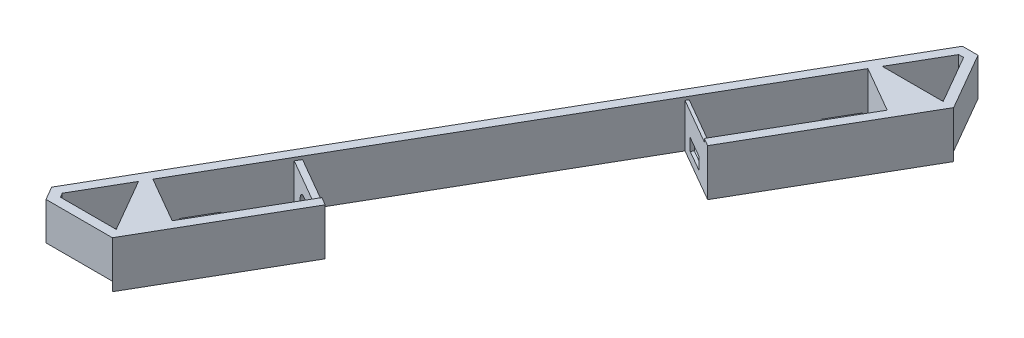
SolidWorks part; units mm, degrees
ref_plane "Front Plane" through (0, 0, 0) normal (0, 0, 1) x (1, 0, 0)
ref_plane "Top Plane" through (0, 0, 0) normal (0, 1, 0) x (1, 0, 0)
ref_plane "Right Plane" through (0, 0, 0) normal (1, 0, 0) x (0, 0, -1)
sketch "Sketch1" plane through (0, 0, 0) normal (0, 1, 0) x (1, 0, 0)
  line L24 (-11.7321, 167.8653) -> (3.2679, 159.2051)
  line L29 (3.2679, 159.2051) -> (-18.2321, 121.966) construction
  line L31 (-107.8246, -1.4282) -> (-108.6491, 0)
  line L40 (-0.8246, 186.7576) -> (0.8246, 186.7576)
  line L41 (-109.5566, -4.4282) -> (-112.1132, 0)
  line L42 (-2.5566, 189.7576) -> (-112.1132, 0)
  line L44 (-2.5566, 189.7576) -> (2.5566, 189.7576)
  line L50 (-99.4737, 15.8923) -> (-89.4737, -1.4282)
  line L51 (-107.8246, -1.4282) -> (-89.4737, -1.4282)
  line L52 (-99.4737, 15.8923) -> (-108.6491, 0)
  line L62 (-10, 170.8653) -> (10, 170.8653)
  line L63 (-10, 170.8653) -> (-0.8246, 186.7576)
  line L64 (0.8246, 186.7576) -> (10, 170.8653)
  line L65 (2.5566, 189.7576) -> (13.4641, 170.8653)
  line L71 (-109.5566, -4.4282) -> (-87.7417, -4.4282)
  line L82 (-39.7369, 84.7186) -> (-37.1388, 83.2186)
  line L96 (13.4641, 170.8653) -> (-16.134, 119.6)
  line L100 (-18.2321, 121.966) -> (-33.2321, 130.6262)
  line L102 (-11.7321, 167.8653) -> (-33.2321, 130.6262)
  line L104 (-33.7321, 129.7602) -> (-97.7417, 18.8923)
  line L111 (-33.7321, 129.7602) -> (-18.7321, 121.1)
  line L113 (-16.134, 119.6) -> (-18.7321, 121.1)
  line L115 (-18.7321, 121.1) -> (-18.2321, 121.966)
  line L117 (-18.2321, 121.966) -> (3.2679, 159.2051)
  line L119 (-33.7321, 129.7602) -> (-33.2321, 130.6262)
  line L121 (-97.7417, 18.8923) -> (-80.7417, 48.3372) construction
  line L123 (-80.7417, 48.3372) -> (-65.7417, 39.6769)
  line L125 (-97.7417, 18.8923) -> (-82.7417, 10.2321)
  line L127 (-82.7417, 10.2321) -> (-65.7417, 39.6769)
  line L133 (-65.7417, 39.6769) -> (-64.7417, 41.409)
  line L134 (-64.7417, 41.409) -> (-79.7417, 50.0692)
  line L135 (-64.7417, 41.409) -> (-62.1436, 39.909)
  line L137 (-87.7417, -4.4282) -> (-62.1436, 39.909)
  dimension "D1" = 43
  dimension "D2" = 34
  dimension "D3" = 2
extrude "Boss-Extrude2" add sketch "Sketch1" along normal blind 15.38 contours L41 L71 L65 L44 L42 L40 L64 L62 L63 L52 L50 L51 L31 region at (-24.4848, 0, -150.4021)
extrude "Boss-Extrude3" add sketch "Sketch1<11>" along normal blind 1 contours L24 L102 L100 | L125 L127 L123 L104 region at (-14.9821, 0, -144.9157) region at (-81.7417, 0, -29.2846)
sketch "Sketch1<11>" plane through (0, 0, 0) normal (0, 1, 0) x (1, 0, 0) same geometry as "Sketch1"
extrude "Boss-Extrude4" add sketch "Sketch1<12>" along normal blind 14.38 contours L119 L111 L115 L100 | L133 L134 L104 L123 region at (-25.9821, 0, -125.8631) region at (-72.7417, 0, -44.8731)
sketch "Sketch1<12>" plane through (0, 0, 0) normal (0, 1, 0) x (1, 0, 0) same geometry as "Sketch1"
sketch "Sketch10" plane through (47.7548, 0, -82.7138) normal (-0.5, 0, 0.866) x (0.866, 0, 0.5)
  line L0 (-94.0929, 0) -> (-85.4329, 0) construction
  line L1 (-73.7724, 0) -> (-94.0929, 0) construction
  line L2 (-85.4329, 0) -> (-85.4329, 3) construction
  line L3 (-85.4329, 3) -> (-81.4329, 3)
  line L4 (-85.4329, 3) -> (-89.4329, 3)
  line L5 (-81.4329, 3) -> (-81.4329, 7)
  line L6 (-89.4329, 3) -> (-89.4329, 7)
  line L7 (-89.4329, 7) -> (-81.4329, 7)
extrude "Cut-Extrude1" cut sketch "Sketch10" against normal blind 8.26
sketch "Sketch12" plane through (1.7452, 0, -3.0228) normal (0.5, 0, -0.866) x (-0.866, 0, -0.5)
  line L0 (94.0929, 0) -> (85.4329, 0) construction
  line L1 (94.0929, 0) -> (73.7724, 0) construction
  line L2 (85.4329, 0) -> (85.4329, 3) construction
  line L3 (85.4329, 3) -> (85.4329, 6.5) construction
  circle A0 centre (85.4329, 6.5) radius 3.5
extrude "Cut-Extrude2" cut sketch "Sketch12" against normal blind 8.26
sketch "Sketch15" plane through (0, 0, 0) normal (0, -1, 0) x (1, 0, 0)
  line L0 (-87.7417, 4.4282) -> (-109.5566, 4.4282)
  line L1 (-109.5566, 4.4282) -> (-112.1132, 0)
  line L2 (-112.1132, 0) -> (-101.2058, -18.8923)
  line L3 (-87.7417, 4.4282) -> (-101.2058, -18.8923)
  line L4 (13.4641, -170.8653) -> (2.5566, -189.7576)
  line L5 (2.5566, -189.7576) -> (-2.5566, -189.7576)
  line L6 (-13.4641, -170.8653) -> (-2.5566, -189.7576)
  line L7 (13.4641, -170.8653) -> (-13.4641, -170.8653)
extrude "Cut-Extrude3" cut sketch "Sketch15" against normal blind 3
sketch "Sketch16" plane through (-84.0849, 0, -48.5465) normal (-0.866, 0, -0.5) x (-0.5, 0, 0.866)
  line L0 (-163.0566, 3) -> (-138.2426, 3) construction
  line L1 (56.0566, 3) -> (26.129, 3) construction
  line L2 (-138.2426, 3) -> (-128.2426, 3)
  line L3 (-138.2426, 3) -> (-138.2426, 1)
  line L4 (-138.2426, 1) -> (-128.2426, 1)
  line L5 (-128.2426, 3) -> (-128.2426, 1)
  line L7 (26.129, 3) -> (16.129, 3)
  line L8 (26.129, 3) -> (26.129, 1)
  line L9 (26.129, 1) -> (16.129, 1)
  line L10 (16.129, 3) -> (16.129, 1)
extrude "Cut-Extrude4" cut sketch "Sketch16" against normal blind 3
